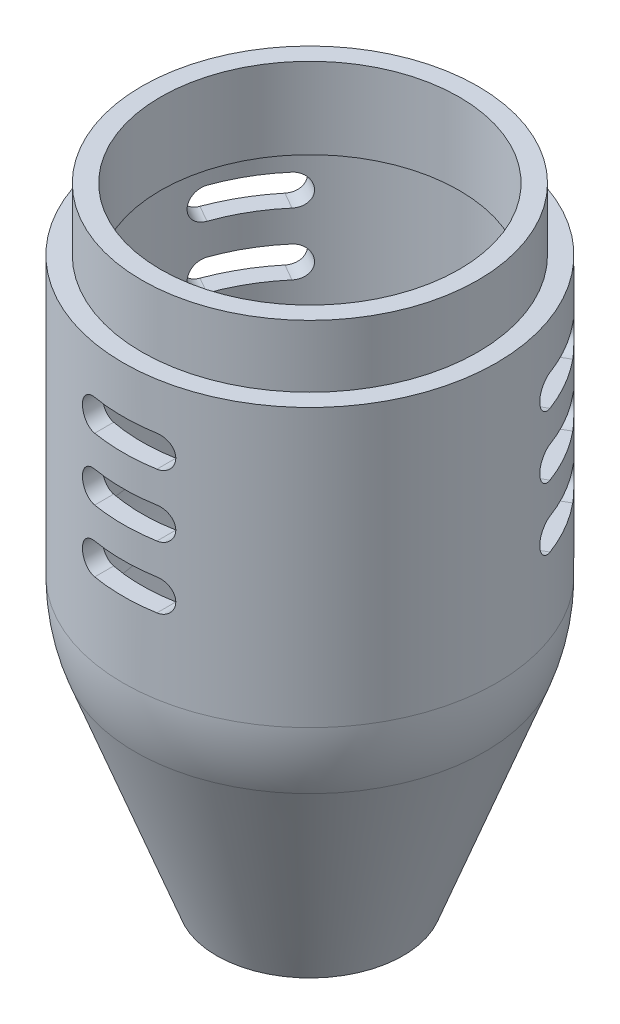
SolidWorks part; units mm, degrees
ref_plane "Alzado" through (0, 0, 0) normal (0, 0, 1) x (1, 0, 0)
ref_plane "Planta" through (0, 0, 0) normal (0, 1, 0) x (1, 0, 0)
ref_plane "Vista lateral" through (0, 0, 0) normal (1, 0, 0) x (0, 0, -1)
sketch "Croquis1" plane through (0, 0, 0) normal (0, 0, 1) x (1, 0, 0)
  line L0 (0, 0) -> (0, 90)
  line L1 (0, 90) -> (30, 90)
  line L2 (30, 90) -> (30, 45.44)
  line L3 (28.0899, 34.9063) -> (15, 0)
  line L4 (15, 0) -> (0, 0)
  arc A0 (28.0899, 34.9063) -> (30, 45.44) centre (0, 45.44) ccw
  point P8 (30, 40)
  dimension "D5" = 30
  dimension "D1" = 90
  dimension "D2" = 30
  dimension "D3" = 15
  dimension "D4" = 50
revolve "Revolución1" add sketch "Croquis1" angle 360 about L0
sketch "Croquis2" plane through (0, 90, 0) normal (0, 1, 0) x (-1, 0, 0)
  circle A2 centre (0, 0) radius 27
  circle A3 centre (0, 0) radius 27
  dimension "D1" = 3
extrude "Extruir-Lámina1" add sketch "Croquis2" along normal blind 10 thin thin type one direction reverse wall 3
shell "Vaciado1" thickness 3 removed face at (0, 0, -15) removed face at (0, 90, 24)
sketch "Croquis3" plane through (0, 0, 0) normal (0, 0, 1) x (1, 0, 0)
  line L0 (0, 0) -> (0, 115) construction
  line L1 (-5, 62.5) -> (5, 62.5)
  line L2 (5, 57.5) -> (0, 57.5)
  line L3 (-5, 57.5) -> (0, 57.5)
  line L4 (-5, 72.5) -> (5, 72.5)
  line L5 (5, 67.5) -> (0, 67.5)
  line L6 (-5, 67.5) -> (0, 67.5)
  line L7 (-5, 82.5) -> (5, 82.5)
  line L8 (5, 77.5) -> (0, 77.5)
  line L9 (-5, 77.5) -> (0, 77.5)
  arc A0 (5, 62.5) -> (5, 57.5) centre (5, 60) cw
  arc A1 (-5, 62.5) -> (-5, 57.5) centre (-5, 60) ccw
  arc A2 (-5, 72.5) -> (-5, 67.5) centre (-5, 70) ccw
  arc A3 (5, 72.5) -> (5, 67.5) centre (5, 70) cw
  arc A4 (-5, 82.5) -> (-5, 77.5) centre (-5, 80) ccw
  arc A5 (5, 82.5) -> (5, 77.5) centre (5, 80) cw
  point P11 (0, 62.5)
  point P12 (13.7577, 56.2147)
  dimension "D2" = 2.5
  dimension "D1" = 5
  dimension "D3" = 10
  dimension "D4" = 60
  dimension "D5" = 5
extrude "Cortar-Extruir1" cut sketch "Croquis3" along normal through all
pattern_circular "MatrizC1" count 3 every 120 about axis through (0, 100, 0) along (0, -1, 0) of "Cortar-Extruir1"
